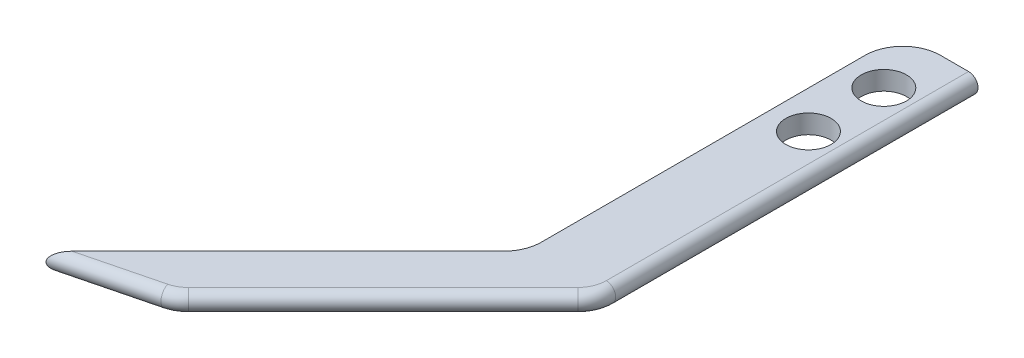
SolidWorks part; units mm, degrees
ref_plane "前视基准面" through (0, 0, 0) normal (0, 0, 1) x (1, 0, 0)
ref_plane "上视基准面" through (0, 0, 0) normal (0, 1, 0) x (1, 0, 0)
ref_plane "右视基准面" through (0, 0, 0) normal (1, 0, 0) x (0, 0, -1)
sketch "草图2" plane through (0, 0, 0) normal (0, 1, 0) x (1, 0, 0)
  line L0 (0, 0) -> (19.9545, 0)
  line L1 (0, 0) -> (0, -100)
  line L2 (19.9545, 0) -> (19.9545, -100.2546)
  line L3 (0, -100) -> (-63.6396, -163.6396)
  line L6 (19.9545, -100.2546) -> (-36.6141, -156.8232)
  line L8 (-36.6141, -156.8232) -> (-63.6396, -163.6396)
  dimension "D1" = 90
  dimension "D2" = 100
  dimension "D3" = 80
extrude "凸台-拉伸2" add sketch "草图2" along normal blind 5
sketch "草图3" plane through (0, 0, 0) normal (0, -1, 0) x (1, 0, 0)
  line L0 (0, 100) -> (19.9545, 100) construction
  line L1 (19.9545, 100.2546) -> (19.9545, 0) construction
  line L2 (9.9772, 100) -> (9.9772, 0) construction
  line L3 (19.9545, 0) -> (0, 0) construction
sketch "草图5" plane through (0, 5, 0) normal (0, 1, 0) x (1, 0, 0)
  line L0 (9.9772, 0) -> (9.9772, -15)
  line L1 (9.9772, -100) -> (9.9772, 0) construction
  line L2 (9.9772, -15) -> (9.9772, -35)
  circle A0 centre (9.9772, -15) radius 6
  circle A1 centre (9.9772, -35) radius 6
  dimension "D2" = 20
  dimension "D1" = 15
extrude "切除-拉伸2" cut sketch "草图5" against normal blind 15 contours A1 | A0
fillet "圆角1" radius 10 1 edges at (0, 2.5, 100) type face fillet first side face at (0, 2.5, 50) second side face at (-31.8198, 2.5, 131.8198)
fillet "圆角2" radius 10 1 edges at (19.9545, 2.5, 100.2546) type face fillet first side face at (19.9545, 2.5, 50.1273) second side face at (-8.3298, 2.5, 128.5389)
fillet "圆角3" radius 10 1 edges at (-36.6141, 2.5, 156.8232) type face fillet first side face at (-9.7943, 2.5, 130.0034) second side face at (-50.1268, 2.5, 160.2314)
fillet "圆角6" radius 10 1 edges at (0, 2.5, 0) type face fillet first side face at (9.9772, 2.5, 0) second side face at (0, 2.5, 47.9289)
fillet "圆角8" 2 edges at (-51.4643, 5, 160.5687) (-51.4643, 0, 160.5687) type full round first side face at (-7.4073, 5, 88.2917) second side face at (9.9772, 0, 41) middle face at (-51.4643, 2.5, 160.5687)
